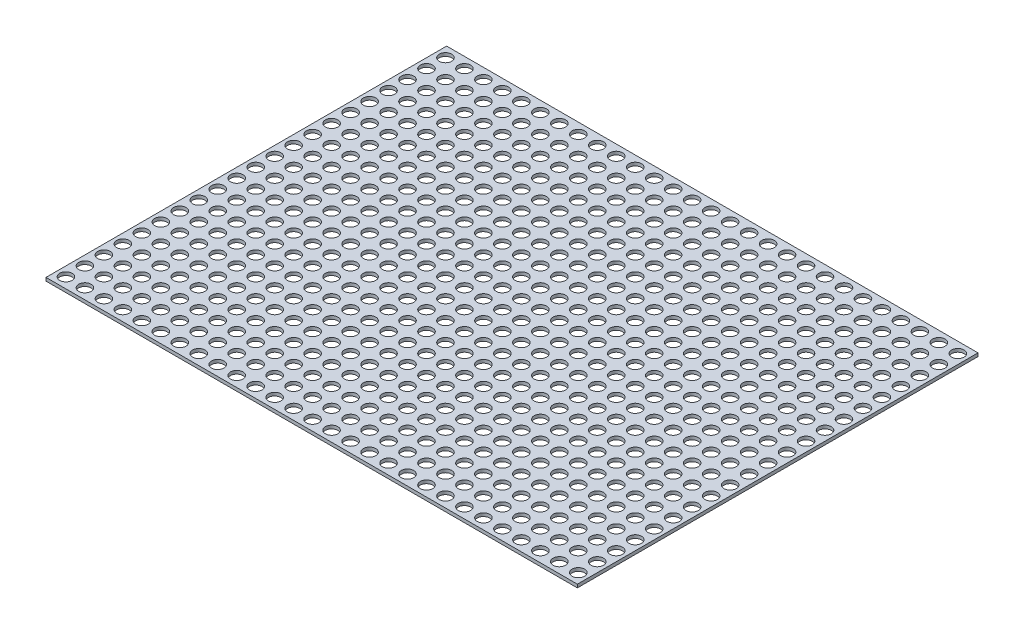
SolidWorks part; units mm, degrees
ref_plane "Front Plane" through (0, 0, 0) normal (0, 0, 1) x (1, 0, 0)
ref_plane "Top Plane" through (0, 0, 0) normal (0, 1, 0) x (1, 0, 0)
ref_plane "Right Plane" through (0, 0, 0) normal (1, 0, 0) x (0, 0, -1)
sketch "Sketch1" plane through (0, 0, 0) normal (0, 1, 0) x (1, 0, 0)
  line L0 (4.5, 4.95) -> (13.5, 4.95) construction
  line L1 (0, 0) -> (252, 0)
  line L2 (0, 0) -> (0, 190)
  line L3 (0, 190) -> (252, 190)
  line L4 (252, 0) -> (252, 190)
  line L5 (4.5, 4.95) -> (4.5, 13.95) construction
  circle A0 centre (4.5, 4.95) radius 2.95
  circle A1 centre (13.5, 4.95) radius 2.95
  circle A2 centre (22.5, 4.95) radius 2.95
  circle A3 centre (31.5, 4.95) radius 2.95
  circle A4 centre (40.5, 4.95) radius 2.95
  circle A5 centre (49.5, 4.95) radius 2.95
  circle A6 centre (58.5, 4.95) radius 2.95
  circle A7 centre (67.5, 4.95) radius 2.95
  circle A8 centre (76.5, 4.95) radius 2.95
  circle A9 centre (85.5, 4.95) radius 2.95
  circle A10 centre (94.5, 4.95) radius 2.95
  circle A11 centre (103.5, 4.95) radius 2.95
  circle A12 centre (112.5, 4.95) radius 2.95
  circle A13 centre (121.5, 4.95) radius 2.95
  circle A14 centre (130.5, 4.95) radius 2.95
  circle A15 centre (139.5, 4.95) radius 2.95
  circle A16 centre (148.5, 4.95) radius 2.95
  circle A17 centre (157.5, 4.95) radius 2.95
  circle A18 centre (166.5, 4.95) radius 2.95
  circle A19 centre (175.5, 4.95) radius 2.95
  circle A20 centre (184.5, 4.95) radius 2.95
  circle A21 centre (193.5, 4.95) radius 2.95
  circle A22 centre (202.5, 4.95) radius 2.95
  circle A23 centre (211.5, 4.95) radius 2.95
  circle A24 centre (220.5, 4.95) radius 2.95
  circle A25 centre (229.5, 4.95) radius 2.95
  circle A26 centre (238.5, 4.95) radius 2.95
  circle A27 centre (247.5, 4.95) radius 2.95
  circle A28 centre (13.5, 13.95) radius 2.95
  circle A29 centre (22.5, 13.95) radius 2.95
  circle A30 centre (31.5, 13.95) radius 2.95
  circle A31 centre (40.5, 13.95) radius 2.95
  circle A32 centre (49.5, 13.95) radius 2.95
  circle A33 centre (58.5, 13.95) radius 2.95
  circle A34 centre (67.5, 13.95) radius 2.95
  circle A35 centre (76.5, 13.95) radius 2.95
  circle A36 centre (85.5, 13.95) radius 2.95
  circle A37 centre (94.5, 13.95) radius 2.95
  circle A38 centre (103.5, 13.95) radius 2.95
  circle A39 centre (112.5, 13.95) radius 2.95
  circle A40 centre (121.5, 13.95) radius 2.95
  circle A41 centre (130.5, 13.95) radius 2.95
  circle A42 centre (139.5, 13.95) radius 2.95
  circle A43 centre (148.5, 13.95) radius 2.95
  circle A44 centre (157.5, 13.95) radius 2.95
  circle A45 centre (166.5, 13.95) radius 2.95
  circle A46 centre (175.5, 13.95) radius 2.95
  circle A47 centre (184.5, 13.95) radius 2.95
  circle A48 centre (193.5, 13.95) radius 2.95
  circle A49 centre (202.5, 13.95) radius 2.95
  circle A50 centre (211.5, 13.95) radius 2.95
  circle A51 centre (220.5, 13.95) radius 2.95
  circle A52 centre (229.5, 13.95) radius 2.95
  circle A53 centre (238.5, 13.95) radius 2.95
  circle A54 centre (247.5, 13.95) radius 2.95
  circle A55 centre (13.5, 22.95) radius 2.95
  circle A56 centre (22.5, 22.95) radius 2.95
  circle A57 centre (31.5, 22.95) radius 2.95
  circle A58 centre (40.5, 22.95) radius 2.95
  circle A59 centre (49.5, 22.95) radius 2.95
  circle A60 centre (58.5, 22.95) radius 2.95
  circle A61 centre (67.5, 22.95) radius 2.95
  circle A62 centre (76.5, 22.95) radius 2.95
  circle A63 centre (85.5, 22.95) radius 2.95
  circle A64 centre (94.5, 22.95) radius 2.95
  circle A65 centre (103.5, 22.95) radius 2.95
  circle A66 centre (112.5, 22.95) radius 2.95
  circle A67 centre (121.5, 22.95) radius 2.95
  circle A68 centre (130.5, 22.95) radius 2.95
  circle A69 centre (139.5, 22.95) radius 2.95
  circle A70 centre (148.5, 22.95) radius 2.95
  circle A71 centre (157.5, 22.95) radius 2.95
  circle A72 centre (166.5, 22.95) radius 2.95
  circle A73 centre (175.5, 22.95) radius 2.95
  circle A74 centre (184.5, 22.95) radius 2.95
  circle A75 centre (193.5, 22.95) radius 2.95
  circle A76 centre (202.5, 22.95) radius 2.95
  circle A77 centre (211.5, 22.95) radius 2.95
  circle A78 centre (220.5, 22.95) radius 2.95
  circle A79 centre (229.5, 22.95) radius 2.95
  circle A80 centre (238.5, 22.95) radius 2.95
  circle A81 centre (247.5, 22.95) radius 2.95
  circle A82 centre (13.5, 31.95) radius 2.95
  circle A83 centre (22.5, 31.95) radius 2.95
  circle A84 centre (31.5, 31.95) radius 2.95
  circle A85 centre (40.5, 31.95) radius 2.95
  circle A86 centre (49.5, 31.95) radius 2.95
  circle A87 centre (58.5, 31.95) radius 2.95
  circle A88 centre (67.5, 31.95) radius 2.95
  circle A89 centre (76.5, 31.95) radius 2.95
  circle A90 centre (85.5, 31.95) radius 2.95
  circle A91 centre (94.5, 31.95) radius 2.95
  circle A92 centre (103.5, 31.95) radius 2.95
  circle A93 centre (112.5, 31.95) radius 2.95
  circle A94 centre (121.5, 31.95) radius 2.95
  circle A95 centre (130.5, 31.95) radius 2.95
  circle A96 centre (139.5, 31.95) radius 2.95
  circle A97 centre (148.5, 31.95) radius 2.95
  circle A98 centre (157.5, 31.95) radius 2.95
  circle A99 centre (166.5, 31.95) radius 2.95
  circle A100 centre (175.5, 31.95) radius 2.95
  circle A101 centre (184.5, 31.95) radius 2.95
  circle A102 centre (193.5, 31.95) radius 2.95
  circle A103 centre (202.5, 31.95) radius 2.95
  circle A104 centre (211.5, 31.95) radius 2.95
  circle A105 centre (220.5, 31.95) radius 2.95
  circle A106 centre (229.5, 31.95) radius 2.95
  circle A107 centre (238.5, 31.95) radius 2.95
  circle A108 centre (247.5, 31.95) radius 2.95
  circle A109 centre (13.5, 40.95) radius 2.95
  circle A110 centre (22.5, 40.95) radius 2.95
  circle A111 centre (31.5, 40.95) radius 2.95
  circle A112 centre (40.5, 40.95) radius 2.95
  circle A113 centre (49.5, 40.95) radius 2.95
  circle A114 centre (58.5, 40.95) radius 2.95
  circle A115 centre (67.5, 40.95) radius 2.95
  circle A116 centre (76.5, 40.95) radius 2.95
  circle A117 centre (85.5, 40.95) radius 2.95
  circle A118 centre (94.5, 40.95) radius 2.95
  circle A119 centre (103.5, 40.95) radius 2.95
  circle A120 centre (112.5, 40.95) radius 2.95
  circle A121 centre (121.5, 40.95) radius 2.95
  circle A122 centre (130.5, 40.95) radius 2.95
  circle A123 centre (139.5, 40.95) radius 2.95
  circle A124 centre (148.5, 40.95) radius 2.95
  circle A125 centre (157.5, 40.95) radius 2.95
  circle A126 centre (166.5, 40.95) radius 2.95
  circle A127 centre (175.5, 40.95) radius 2.95
  circle A128 centre (184.5, 40.95) radius 2.95
  circle A129 centre (193.5, 40.95) radius 2.95
  circle A130 centre (202.5, 40.95) radius 2.95
  circle A131 centre (211.5, 40.95) radius 2.95
  circle A132 centre (220.5, 40.95) radius 2.95
  circle A133 centre (229.5, 40.95) radius 2.95
  circle A134 centre (238.5, 40.95) radius 2.95
  circle A135 centre (247.5, 40.95) radius 2.95
  circle A136 centre (13.5, 49.95) radius 2.95
  circle A137 centre (22.5, 49.95) radius 2.95
  circle A138 centre (31.5, 49.95) radius 2.95
  circle A139 centre (40.5, 49.95) radius 2.95
  circle A140 centre (49.5, 49.95) radius 2.95
  circle A141 centre (58.5, 49.95) radius 2.95
  circle A142 centre (67.5, 49.95) radius 2.95
  circle A143 centre (76.5, 49.95) radius 2.95
  circle A144 centre (85.5, 49.95) radius 2.95
  circle A145 centre (94.5, 49.95) radius 2.95
  circle A146 centre (103.5, 49.95) radius 2.95
  circle A147 centre (112.5, 49.95) radius 2.95
  circle A148 centre (121.5, 49.95) radius 2.95
  circle A149 centre (130.5, 49.95) radius 2.95
  circle A150 centre (139.5, 49.95) radius 2.95
  circle A151 centre (148.5, 49.95) radius 2.95
  circle A152 centre (157.5, 49.95) radius 2.95
  circle A153 centre (166.5, 49.95) radius 2.95
  circle A154 centre (175.5, 49.95) radius 2.95
  circle A155 centre (184.5, 49.95) radius 2.95
  circle A156 centre (193.5, 49.95) radius 2.95
  circle A157 centre (202.5, 49.95) radius 2.95
  circle A158 centre (211.5, 49.95) radius 2.95
  circle A159 centre (220.5, 49.95) radius 2.95
  circle A160 centre (229.5, 49.95) radius 2.95
  circle A161 centre (238.5, 49.95) radius 2.95
  circle A162 centre (247.5, 49.95) radius 2.95
  circle A163 centre (13.5, 58.95) radius 2.95
  circle A164 centre (22.5, 58.95) radius 2.95
  circle A165 centre (31.5, 58.95) radius 2.95
  circle A166 centre (40.5, 58.95) radius 2.95
  circle A167 centre (49.5, 58.95) radius 2.95
  circle A168 centre (58.5, 58.95) radius 2.95
  circle A169 centre (67.5, 58.95) radius 2.95
  circle A170 centre (76.5, 58.95) radius 2.95
  circle A171 centre (85.5, 58.95) radius 2.95
  circle A172 centre (94.5, 58.95) radius 2.95
  circle A173 centre (103.5, 58.95) radius 2.95
  circle A174 centre (112.5, 58.95) radius 2.95
  circle A175 centre (121.5, 58.95) radius 2.95
  circle A176 centre (130.5, 58.95) radius 2.95
  circle A177 centre (139.5, 58.95) radius 2.95
  circle A178 centre (148.5, 58.95) radius 2.95
  circle A179 centre (157.5, 58.95) radius 2.95
  circle A180 centre (166.5, 58.95) radius 2.95
  circle A181 centre (175.5, 58.95) radius 2.95
  circle A182 centre (184.5, 58.95) radius 2.95
  circle A183 centre (193.5, 58.95) radius 2.95
  circle A184 centre (202.5, 58.95) radius 2.95
  circle A185 centre (211.5, 58.95) radius 2.95
  circle A186 centre (220.5, 58.95) radius 2.95
  circle A187 centre (229.5, 58.95) radius 2.95
  circle A188 centre (238.5, 58.95) radius 2.95
  circle A189 centre (247.5, 58.95) radius 2.95
  circle A190 centre (13.5, 67.95) radius 2.95
  circle A191 centre (22.5, 67.95) radius 2.95
  circle A192 centre (31.5, 67.95) radius 2.95
  circle A193 centre (40.5, 67.95) radius 2.95
  circle A194 centre (49.5, 67.95) radius 2.95
  circle A195 centre (58.5, 67.95) radius 2.95
  circle A196 centre (67.5, 67.95) radius 2.95
  circle A197 centre (76.5, 67.95) radius 2.95
  circle A198 centre (85.5, 67.95) radius 2.95
  circle A199 centre (94.5, 67.95) radius 2.95
  circle A200 centre (103.5, 67.95) radius 2.95
  circle A201 centre (112.5, 67.95) radius 2.95
  circle A202 centre (121.5, 67.95) radius 2.95
  circle A203 centre (130.5, 67.95) radius 2.95
  circle A204 centre (139.5, 67.95) radius 2.95
  circle A205 centre (148.5, 67.95) radius 2.95
  circle A206 centre (157.5, 67.95) radius 2.95
  circle A207 centre (166.5, 67.95) radius 2.95
  circle A208 centre (175.5, 67.95) radius 2.95
  circle A209 centre (184.5, 67.95) radius 2.95
  circle A210 centre (193.5, 67.95) radius 2.95
  circle A211 centre (202.5, 67.95) radius 2.95
  circle A212 centre (211.5, 67.95) radius 2.95
  circle A213 centre (220.5, 67.95) radius 2.95
  circle A214 centre (229.5, 67.95) radius 2.95
  circle A215 centre (238.5, 67.95) radius 2.95
  circle A216 centre (247.5, 67.95) radius 2.95
  circle A217 centre (13.5, 76.95) radius 2.95
  circle A218 centre (22.5, 76.95) radius 2.95
  circle A219 centre (31.5, 76.95) radius 2.95
  circle A220 centre (40.5, 76.95) radius 2.95
  circle A221 centre (49.5, 76.95) radius 2.95
  circle A222 centre (58.5, 76.95) radius 2.95
  circle A223 centre (67.5, 76.95) radius 2.95
  circle A224 centre (76.5, 76.95) radius 2.95
  circle A225 centre (85.5, 76.95) radius 2.95
  circle A226 centre (94.5, 76.95) radius 2.95
  circle A227 centre (103.5, 76.95) radius 2.95
  circle A228 centre (112.5, 76.95) radius 2.95
  circle A229 centre (121.5, 76.95) radius 2.95
  circle A230 centre (130.5, 76.95) radius 2.95
  circle A231 centre (139.5, 76.95) radius 2.95
  circle A232 centre (148.5, 76.95) radius 2.95
  circle A233 centre (157.5, 76.95) radius 2.95
  circle A234 centre (166.5, 76.95) radius 2.95
  circle A235 centre (175.5, 76.95) radius 2.95
  circle A236 centre (184.5, 76.95) radius 2.95
  circle A237 centre (193.5, 76.95) radius 2.95
  circle A238 centre (202.5, 76.95) radius 2.95
  circle A239 centre (211.5, 76.95) radius 2.95
  circle A240 centre (220.5, 76.95) radius 2.95
  circle A241 centre (229.5, 76.95) radius 2.95
  circle A242 centre (238.5, 76.95) radius 2.95
  circle A243 centre (247.5, 76.95) radius 2.95
  circle A244 centre (13.5, 85.95) radius 2.95
  circle A245 centre (22.5, 85.95) radius 2.95
  circle A246 centre (31.5, 85.95) radius 2.95
  circle A247 centre (40.5, 85.95) radius 2.95
  circle A248 centre (49.5, 85.95) radius 2.95
  circle A249 centre (58.5, 85.95) radius 2.95
  circle A250 centre (67.5, 85.95) radius 2.95
  circle A251 centre (76.5, 85.95) radius 2.95
  circle A252 centre (85.5, 85.95) radius 2.95
  circle A253 centre (94.5, 85.95) radius 2.95
  circle A254 centre (103.5, 85.95) radius 2.95
  circle A255 centre (112.5, 85.95) radius 2.95
  circle A256 centre (121.5, 85.95) radius 2.95
  circle A257 centre (130.5, 85.95) radius 2.95
  circle A258 centre (139.5, 85.95) radius 2.95
  circle A259 centre (148.5, 85.95) radius 2.95
  circle A260 centre (157.5, 85.95) radius 2.95
  circle A261 centre (166.5, 85.95) radius 2.95
  circle A262 centre (175.5, 85.95) radius 2.95
  circle A263 centre (184.5, 85.95) radius 2.95
  circle A264 centre (193.5, 85.95) radius 2.95
  circle A265 centre (202.5, 85.95) radius 2.95
  circle A266 centre (211.5, 85.95) radius 2.95
  circle A267 centre (220.5, 85.95) radius 2.95
  circle A268 centre (229.5, 85.95) radius 2.95
  circle A269 centre (238.5, 85.95) radius 2.95
  circle A270 centre (247.5, 85.95) radius 2.95
  circle A271 centre (13.5, 94.95) radius 2.95
  circle A272 centre (22.5, 94.95) radius 2.95
  circle A273 centre (31.5, 94.95) radius 2.95
  circle A274 centre (40.5, 94.95) radius 2.95
  circle A275 centre (49.5, 94.95) radius 2.95
  circle A276 centre (58.5, 94.95) radius 2.95
  circle A277 centre (67.5, 94.95) radius 2.95
  circle A278 centre (76.5, 94.95) radius 2.95
  circle A279 centre (85.5, 94.95) radius 2.95
  circle A280 centre (94.5, 94.95) radius 2.95
  circle A281 centre (103.5, 94.95) radius 2.95
  circle A282 centre (112.5, 94.95) radius 2.95
  circle A283 centre (121.5, 94.95) radius 2.95
  circle A284 centre (130.5, 94.95) radius 2.95
  circle A285 centre (139.5, 94.95) radius 2.95
  circle A286 centre (148.5, 94.95) radius 2.95
  circle A287 centre (157.5, 94.95) radius 2.95
  circle A288 centre (166.5, 94.95) radius 2.95
  circle A289 centre (175.5, 94.95) radius 2.95
  circle A290 centre (184.5, 94.95) radius 2.95
  circle A291 centre (193.5, 94.95) radius 2.95
  circle A292 centre (202.5, 94.95) radius 2.95
  circle A293 centre (211.5, 94.95) radius 2.95
  circle A294 centre (220.5, 94.95) radius 2.95
  circle A295 centre (229.5, 94.95) radius 2.95
  circle A296 centre (238.5, 94.95) radius 2.95
  circle A297 centre (247.5, 94.95) radius 2.95
  circle A298 centre (13.5, 103.95) radius 2.95
  circle A299 centre (22.5, 103.95) radius 2.95
  circle A300 centre (31.5, 103.95) radius 2.95
  circle A301 centre (40.5, 103.95) radius 2.95
  circle A302 centre (49.5, 103.95) radius 2.95
  circle A303 centre (58.5, 103.95) radius 2.95
  circle A304 centre (67.5, 103.95) radius 2.95
  circle A305 centre (76.5, 103.95) radius 2.95
  circle A306 centre (85.5, 103.95) radius 2.95
  circle A307 centre (94.5, 103.95) radius 2.95
  circle A308 centre (103.5, 103.95) radius 2.95
  circle A309 centre (112.5, 103.95) radius 2.95
  circle A310 centre (121.5, 103.95) radius 2.95
  circle A311 centre (130.5, 103.95) radius 2.95
  circle A312 centre (139.5, 103.95) radius 2.95
  circle A313 centre (148.5, 103.95) radius 2.95
  circle A314 centre (157.5, 103.95) radius 2.95
  circle A315 centre (166.5, 103.95) radius 2.95
  circle A316 centre (175.5, 103.95) radius 2.95
  circle A317 centre (184.5, 103.95) radius 2.95
  circle A318 centre (193.5, 103.95) radius 2.95
  circle A319 centre (202.5, 103.95) radius 2.95
  circle A320 centre (211.5, 103.95) radius 2.95
  circle A321 centre (220.5, 103.95) radius 2.95
  circle A322 centre (229.5, 103.95) radius 2.95
  circle A323 centre (238.5, 103.95) radius 2.95
  circle A324 centre (247.5, 103.95) radius 2.95
  circle A325 centre (13.5, 112.95) radius 2.95
  circle A326 centre (22.5, 112.95) radius 2.95
  circle A327 centre (31.5, 112.95) radius 2.95
  circle A328 centre (40.5, 112.95) radius 2.95
  circle A329 centre (49.5, 112.95) radius 2.95
  circle A330 centre (58.5, 112.95) radius 2.95
  circle A331 centre (67.5, 112.95) radius 2.95
  circle A332 centre (76.5, 112.95) radius 2.95
  circle A333 centre (85.5, 112.95) radius 2.95
  circle A334 centre (94.5, 112.95) radius 2.95
  circle A335 centre (103.5, 112.95) radius 2.95
  circle A336 centre (112.5, 112.95) radius 2.95
  circle A337 centre (121.5, 112.95) radius 2.95
  circle A338 centre (130.5, 112.95) radius 2.95
  circle A339 centre (139.5, 112.95) radius 2.95
  circle A340 centre (148.5, 112.95) radius 2.95
  circle A341 centre (157.5, 112.95) radius 2.95
  circle A342 centre (166.5, 112.95) radius 2.95
  circle A343 centre (175.5, 112.95) radius 2.95
  circle A344 centre (184.5, 112.95) radius 2.95
  circle A345 centre (193.5, 112.95) radius 2.95
  circle A346 centre (202.5, 112.95) radius 2.95
  circle A347 centre (211.5, 112.95) radius 2.95
  circle A348 centre (220.5, 112.95) radius 2.95
  circle A349 centre (229.5, 112.95) radius 2.95
  circle A350 centre (238.5, 112.95) radius 2.95
  circle A351 centre (247.5, 112.95) radius 2.95
  circle A352 centre (13.5, 121.95) radius 2.95
  circle A353 centre (22.5, 121.95) radius 2.95
  circle A354 centre (31.5, 121.95) radius 2.95
  circle A355 centre (40.5, 121.95) radius 2.95
  circle A356 centre (49.5, 121.95) radius 2.95
  circle A357 centre (58.5, 121.95) radius 2.95
  circle A358 centre (67.5, 121.95) radius 2.95
  circle A359 centre (76.5, 121.95) radius 2.95
  circle A360 centre (85.5, 121.95) radius 2.95
  circle A361 centre (94.5, 121.95) radius 2.95
  circle A362 centre (103.5, 121.95) radius 2.95
  circle A363 centre (112.5, 121.95) radius 2.95
  circle A364 centre (121.5, 121.95) radius 2.95
  circle A365 centre (130.5, 121.95) radius 2.95
  circle A366 centre (139.5, 121.95) radius 2.95
  circle A367 centre (148.5, 121.95) radius 2.95
  circle A368 centre (157.5, 121.95) radius 2.95
  circle A369 centre (166.5, 121.95) radius 2.95
  circle A370 centre (175.5, 121.95) radius 2.95
  circle A371 centre (184.5, 121.95) radius 2.95
  circle A372 centre (193.5, 121.95) radius 2.95
  circle A373 centre (202.5, 121.95) radius 2.95
  circle A374 centre (211.5, 121.95) radius 2.95
  circle A375 centre (220.5, 121.95) radius 2.95
  circle A376 centre (229.5, 121.95) radius 2.95
  circle A377 centre (238.5, 121.95) radius 2.95
  circle A378 centre (247.5, 121.95) radius 2.95
  circle A379 centre (13.5, 130.95) radius 2.95
  circle A380 centre (22.5, 130.95) radius 2.95
  circle A381 centre (31.5, 130.95) radius 2.95
  circle A382 centre (40.5, 130.95) radius 2.95
  circle A383 centre (49.5, 130.95) radius 2.95
  circle A384 centre (58.5, 130.95) radius 2.95
  circle A385 centre (67.5, 130.95) radius 2.95
  circle A386 centre (76.5, 130.95) radius 2.95
  circle A387 centre (85.5, 130.95) radius 2.95
  circle A388 centre (94.5, 130.95) radius 2.95
  circle A389 centre (103.5, 130.95) radius 2.95
  circle A390 centre (112.5, 130.95) radius 2.95
  circle A391 centre (121.5, 130.95) radius 2.95
  circle A392 centre (130.5, 130.95) radius 2.95
  circle A393 centre (139.5, 130.95) radius 2.95
  circle A394 centre (148.5, 130.95) radius 2.95
  circle A395 centre (157.5, 130.95) radius 2.95
  circle A396 centre (166.5, 130.95) radius 2.95
  circle A397 centre (175.5, 130.95) radius 2.95
  circle A398 centre (184.5, 130.95) radius 2.95
  circle A399 centre (193.5, 130.95) radius 2.95
  circle A400 centre (202.5, 130.95) radius 2.95
  circle A401 centre (211.5, 130.95) radius 2.95
  circle A402 centre (220.5, 130.95) radius 2.95
  circle A403 centre (229.5, 130.95) radius 2.95
  circle A404 centre (238.5, 130.95) radius 2.95
  circle A405 centre (247.5, 130.95) radius 2.95
  circle A406 centre (13.5, 139.95) radius 2.95
  circle A407 centre (22.5, 139.95) radius 2.95
  circle A408 centre (31.5, 139.95) radius 2.95
  circle A409 centre (40.5, 139.95) radius 2.95
  circle A410 centre (49.5, 139.95) radius 2.95
  circle A411 centre (58.5, 139.95) radius 2.95
  circle A412 centre (67.5, 139.95) radius 2.95
  circle A413 centre (76.5, 139.95) radius 2.95
  circle A414 centre (85.5, 139.95) radius 2.95
  circle A415 centre (94.5, 139.95) radius 2.95
  circle A416 centre (103.5, 139.95) radius 2.95
  circle A417 centre (112.5, 139.95) radius 2.95
  circle A418 centre (121.5, 139.95) radius 2.95
  circle A419 centre (130.5, 139.95) radius 2.95
  circle A420 centre (139.5, 139.95) radius 2.95
  circle A421 centre (148.5, 139.95) radius 2.95
  circle A422 centre (157.5, 139.95) radius 2.95
  circle A423 centre (166.5, 139.95) radius 2.95
  circle A424 centre (175.5, 139.95) radius 2.95
  circle A425 centre (184.5, 139.95) radius 2.95
  circle A426 centre (193.5, 139.95) radius 2.95
  circle A427 centre (202.5, 139.95) radius 2.95
  circle A428 centre (211.5, 139.95) radius 2.95
  circle A429 centre (220.5, 139.95) radius 2.95
  circle A430 centre (229.5, 139.95) radius 2.95
  circle A431 centre (238.5, 139.95) radius 2.95
  circle A432 centre (247.5, 139.95) radius 2.95
  circle A433 centre (13.5, 148.95) radius 2.95
  circle A434 centre (22.5, 148.95) radius 2.95
  circle A435 centre (31.5, 148.95) radius 2.95
  circle A436 centre (40.5, 148.95) radius 2.95
  circle A437 centre (49.5, 148.95) radius 2.95
  circle A438 centre (58.5, 148.95) radius 2.95
  circle A439 centre (67.5, 148.95) radius 2.95
  circle A440 centre (76.5, 148.95) radius 2.95
  circle A441 centre (85.5, 148.95) radius 2.95
  circle A442 centre (94.5, 148.95) radius 2.95
  circle A443 centre (103.5, 148.95) radius 2.95
  circle A444 centre (112.5, 148.95) radius 2.95
  circle A445 centre (121.5, 148.95) radius 2.95
  circle A446 centre (130.5, 148.95) radius 2.95
  circle A447 centre (139.5, 148.95) radius 2.95
  circle A448 centre (148.5, 148.95) radius 2.95
  circle A449 centre (157.5, 148.95) radius 2.95
  circle A450 centre (166.5, 148.95) radius 2.95
  circle A451 centre (175.5, 148.95) radius 2.95
  circle A452 centre (184.5, 148.95) radius 2.95
  circle A453 centre (193.5, 148.95) radius 2.95
  circle A454 centre (202.5, 148.95) radius 2.95
  circle A455 centre (211.5, 148.95) radius 2.95
  circle A456 centre (220.5, 148.95) radius 2.95
  circle A457 centre (229.5, 148.95) radius 2.95
  circle A458 centre (238.5, 148.95) radius 2.95
  circle A459 centre (247.5, 148.95) radius 2.95
  circle A460 centre (13.5, 157.95) radius 2.95
  circle A461 centre (22.5, 157.95) radius 2.95
  circle A462 centre (31.5, 157.95) radius 2.95
  circle A463 centre (40.5, 157.95) radius 2.95
  circle A464 centre (49.5, 157.95) radius 2.95
  circle A465 centre (58.5, 157.95) radius 2.95
  circle A466 centre (67.5, 157.95) radius 2.95
  circle A467 centre (76.5, 157.95) radius 2.95
  circle A468 centre (85.5, 157.95) radius 2.95
  circle A469 centre (94.5, 157.95) radius 2.95
  circle A470 centre (103.5, 157.95) radius 2.95
  circle A471 centre (112.5, 157.95) radius 2.95
  circle A472 centre (121.5, 157.95) radius 2.95
  circle A473 centre (130.5, 157.95) radius 2.95
  circle A474 centre (139.5, 157.95) radius 2.95
  circle A475 centre (148.5, 157.95) radius 2.95
  circle A476 centre (157.5, 157.95) radius 2.95
  circle A477 centre (166.5, 157.95) radius 2.95
  circle A478 centre (175.5, 157.95) radius 2.95
  circle A479 centre (184.5, 157.95) radius 2.95
  circle A480 centre (193.5, 157.95) radius 2.95
  circle A481 centre (202.5, 157.95) radius 2.95
  circle A482 centre (211.5, 157.95) radius 2.95
  circle A483 centre (220.5, 157.95) radius 2.95
  circle A484 centre (229.5, 157.95) radius 2.95
  circle A485 centre (238.5, 157.95) radius 2.95
  circle A486 centre (247.5, 157.95) radius 2.95
  circle A487 centre (13.5, 166.95) radius 2.95
  circle A488 centre (22.5, 166.95) radius 2.95
  circle A489 centre (31.5, 166.95) radius 2.95
  circle A490 centre (40.5, 166.95) radius 2.95
  circle A491 centre (49.5, 166.95) radius 2.95
  circle A492 centre (58.5, 166.95) radius 2.95
  circle A493 centre (67.5, 166.95) radius 2.95
  circle A494 centre (76.5, 166.95) radius 2.95
  circle A495 centre (85.5, 166.95) radius 2.95
  circle A496 centre (94.5, 166.95) radius 2.95
  circle A497 centre (103.5, 166.95) radius 2.95
  circle A498 centre (112.5, 166.95) radius 2.95
  circle A499 centre (121.5, 166.95) radius 2.95
  circle A500 centre (130.5, 166.95) radius 2.95
  circle A501 centre (139.5, 166.95) radius 2.95
  circle A502 centre (148.5, 166.95) radius 2.95
  circle A503 centre (157.5, 166.95) radius 2.95
  circle A504 centre (166.5, 166.95) radius 2.95
  circle A505 centre (175.5, 166.95) radius 2.95
  circle A506 centre (184.5, 166.95) radius 2.95
  circle A507 centre (193.5, 166.95) radius 2.95
  circle A508 centre (202.5, 166.95) radius 2.95
  circle A509 centre (211.5, 166.95) radius 2.95
  circle A510 centre (220.5, 166.95) radius 2.95
  circle A511 centre (229.5, 166.95) radius 2.95
  circle A512 centre (238.5, 166.95) radius 2.95
  circle A513 centre (247.5, 166.95) radius 2.95
  circle A514 centre (13.5, 175.95) radius 2.95
  circle A515 centre (22.5, 175.95) radius 2.95
  circle A516 centre (31.5, 175.95) radius 2.95
  circle A517 centre (40.5, 175.95) radius 2.95
  circle A518 centre (49.5, 175.95) radius 2.95
  circle A519 centre (58.5, 175.95) radius 2.95
  circle A520 centre (67.5, 175.95) radius 2.95
  circle A521 centre (76.5, 175.95) radius 2.95
  circle A522 centre (85.5, 175.95) radius 2.95
  circle A523 centre (94.5, 175.95) radius 2.95
  circle A524 centre (103.5, 175.95) radius 2.95
  circle A525 centre (112.5, 175.95) radius 2.95
  circle A526 centre (121.5, 175.95) radius 2.95
  circle A527 centre (130.5, 175.95) radius 2.95
  circle A528 centre (139.5, 175.95) radius 2.95
  circle A529 centre (148.5, 175.95) radius 2.95
  circle A530 centre (157.5, 175.95) radius 2.95
  circle A531 centre (166.5, 175.95) radius 2.95
  circle A532 centre (175.5, 175.95) radius 2.95
  circle A533 centre (184.5, 175.95) radius 2.95
  circle A534 centre (193.5, 175.95) radius 2.95
  circle A535 centre (202.5, 175.95) radius 2.95
  circle A536 centre (211.5, 175.95) radius 2.95
  circle A537 centre (220.5, 175.95) radius 2.95
  circle A538 centre (229.5, 175.95) radius 2.95
  circle A539 centre (238.5, 175.95) radius 2.95
  circle A540 centre (247.5, 175.95) radius 2.95
  circle A541 centre (13.5, 184.95) radius 2.95
  circle A542 centre (22.5, 184.95) radius 2.95
  circle A543 centre (31.5, 184.95) radius 2.95
  circle A544 centre (40.5, 184.95) radius 2.95
  circle A545 centre (49.5, 184.95) radius 2.95
  circle A546 centre (58.5, 184.95) radius 2.95
  circle A547 centre (67.5, 184.95) radius 2.95
  circle A548 centre (76.5, 184.95) radius 2.95
  circle A549 centre (85.5, 184.95) radius 2.95
  circle A550 centre (94.5, 184.95) radius 2.95
  circle A551 centre (103.5, 184.95) radius 2.95
  circle A552 centre (112.5, 184.95) radius 2.95
  circle A553 centre (121.5, 184.95) radius 2.95
  circle A554 centre (130.5, 184.95) radius 2.95
  circle A555 centre (139.5, 184.95) radius 2.95
  circle A556 centre (148.5, 184.95) radius 2.95
  circle A557 centre (157.5, 184.95) radius 2.95
  circle A558 centre (166.5, 184.95) radius 2.95
  circle A559 centre (175.5, 184.95) radius 2.95
  circle A560 centre (184.5, 184.95) radius 2.95
  circle A561 centre (193.5, 184.95) radius 2.95
  circle A562 centre (202.5, 184.95) radius 2.95
  circle A563 centre (211.5, 184.95) radius 2.95
  circle A564 centre (220.5, 184.95) radius 2.95
  circle A565 centre (229.5, 184.95) radius 2.95
  circle A566 centre (238.5, 184.95) radius 2.95
  circle A567 centre (247.5, 184.95) radius 2.95
  circle A568 centre (4.5, 13.95) radius 2.95
  circle A569 centre (4.5, 22.95) radius 2.95
  circle A570 centre (4.5, 31.95) radius 2.95
  circle A571 centre (4.5, 40.95) radius 2.95
  circle A572 centre (4.5, 49.95) radius 2.95
  circle A573 centre (4.5, 58.95) radius 2.95
  circle A574 centre (4.5, 67.95) radius 2.95
  circle A575 centre (4.5, 76.95) radius 2.95
  circle A576 centre (4.5, 85.95) radius 2.95
  circle A577 centre (4.5, 94.95) radius 2.95
  circle A578 centre (4.5, 103.95) radius 2.95
  circle A579 centre (4.5, 112.95) radius 2.95
  circle A580 centre (4.5, 121.95) radius 2.95
  circle A581 centre (4.5, 130.95) radius 2.95
  circle A582 centre (4.5, 139.95) radius 2.95
  circle A583 centre (4.5, 148.95) radius 2.95
  circle A584 centre (4.5, 157.95) radius 2.95
  circle A585 centre (4.5, 166.95) radius 2.95
  circle A586 centre (4.5, 175.95) radius 2.95
  circle A587 centre (4.5, 184.95) radius 2.95
  dimension "D3" = 5.9
  dimension "D1" = 252
  dimension "D2" = 190
  dimension "D4" = 4.95
  dimension "D5" = 4.5
  dimension "D8" = 9
  dimension "D9" = 9
  dimension "D6" = 28
  dimension "D7" = 21
extrude "Boss-Extrude1" add sketch "Sketch1" along normal blind 1.55 contours L1 L4 L3 L2 A587 A586 A585 A584 A583 A582 A581 A580 A579 A578 A577 A576 A575 A574 A573 A572 A571 A570 A569 A568 A567 A566 A565 region at (126, 0, -95.0253)
equation "\"Length\"= 283"
equation "\"Width\"= 225"
equation "\"WallThickness\"= 12.5"
equation "\"UpperWaterJacketThickness\"= 28"
equation "\"SpacerHeight\"= 80.2"
equation "\"PlateLength\"=252"
equation "\"D1@Sketch1\"=\"PlateLength\""
equation "\"PlateWidth\"=190"
equation "\"D2@Sketch1\"=\"PlateWidth\""
equation "\"PlateHoleDiameter\"=5.9"
equation "\"D3@Sketch1\"=\"PlateHoleDiameter\""
equation "\"PlateHoleBottom\"= 2"
equation "\"D4@Sketch1\"=\"PlateHoleBottom\"+\"PlateHoleDiameter\"/2"
equation "\"PlateHoleSide\"= 1.55"
equation "\"D5@Sketch1\"=\"PlateHoleSide\"+\"PlateHoleDiameter\"/2"
equation "\"PlateHoleSpacing\"= 3.1"
equation "\"D8@Sketch1\"=\"PlateHoleSpacing\"+\"PlateHoleDiameter\""
equation "\"D9@Sketch1\"=\"PlateHoleSpacing\"+\"PlateHoleDiameter\""
equation "\"PlateThickness\"=1.55"
equation "\"D1@Boss-Extrude1\"=\"PlateThickness\""
